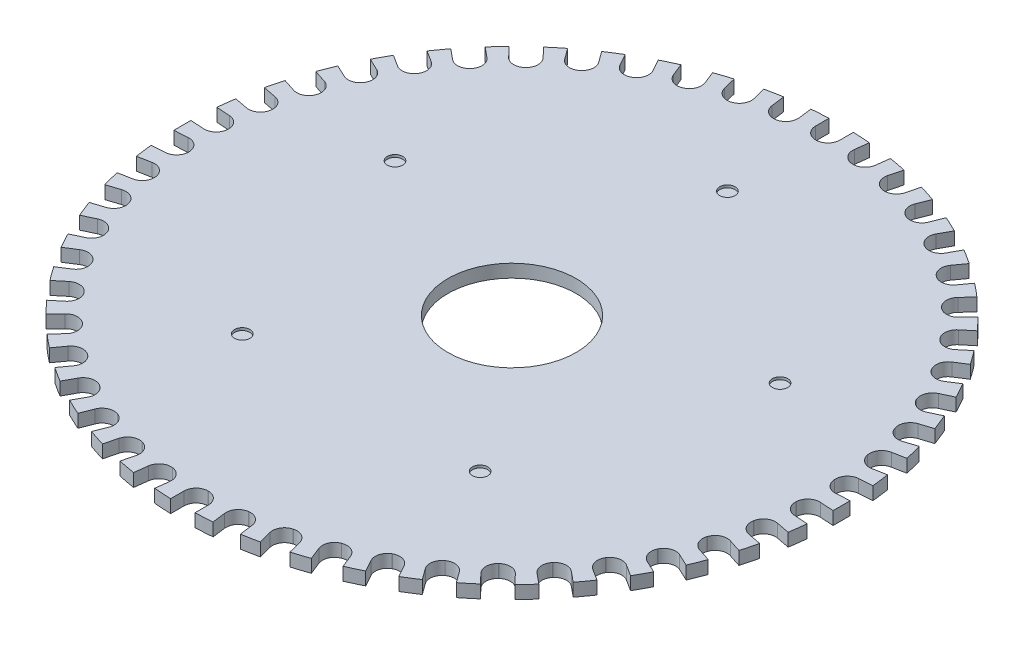
SolidWorks part; units mm, degrees
material "AISI 304"
ref_plane "Plano frontal" through (0, 0, 0) normal (0, 0, 1) x (1, 0, 0)
ref_plane "Plano superior" through (0, 0, 0) normal (0, 1, 0) x (1, 0, 0)
ref_plane "Plano direito" through (0, 0, 0) normal (1, 0, 0) x (0, 0, -1)
sketch "Esboço1" plane through (0, 0, 0) normal (0, 1, 0) x (1, 0, 0)
  line L0 (1.1332, 12.7999) -> (1.0679, 12.283)
  line L1 (-0.48, 12.841) -> (-0.48, 12.32)
  line L2 (0.47, 12.8414) -> (0.47, 12.32)
  line L3 (-0.01, 11.85) -> (0, 11.85)
  line L4 (2.0757, 12.6812) -> (2.0104, 12.1639)
  line L5 (1.4753, 11.7578) -> (1.4852, 11.7566)
  line L6 (2.7285, 12.557) -> (2.5989, 12.0523)
  line L7 (3.6488, 12.3211) -> (3.5191, 11.8161)
  line L8 (2.9373, 11.4802) -> (2.947, 11.4777)
  line L9 (4.2808, 12.116) -> (4.089, 11.6315)
  line L10 (5.1642, 11.7666) -> (4.9723, 11.2818)
  line L11 (4.353, 11.0215) -> (4.3623, 11.0179)
  line L12 (5.7656, 11.4839) -> (5.5146, 11.0273)
  line L13 (6.5983, 11.0266) -> (6.3471, 10.5697)
  line L14 (5.7, 10.3891) -> (5.7088, 10.3842)
  line L15 (7.1594, 10.6707) -> (6.8532, 10.2492)
  line L16 (7.9282, 10.1127) -> (7.6218, 9.6908)
  line L17 (6.9572, 9.5927) -> (6.9653, 9.5869)
  line L18 (8.4404, 9.6893) -> (8.0837, 9.3095)
  line L19 (9.1332, 9.0392) -> (8.7762, 8.6592)
  line L20 (8.1046, 8.6451) -> (8.1119, 8.6383)
  line L21 (9.5882, 8.555) -> (9.1868, 8.2229)
  line L22 (10.1941, 7.8233) -> (9.7923, 7.4909)
  line L23 (9.1242, 7.5612) -> (9.1306, 7.5535)
  line L24 (10.5848, 7.2858) -> (10.1449, 7.0067)
  line L25 (11.0942, 6.4839) -> (10.654, 6.2046)
  line L26 (9.9999, 6.358) -> (10.0053, 6.3495)
  line L27 (11.4145, 5.9018) -> (10.9431, 5.6799)
  line L28 (11.8194, 5.0423) -> (11.3476, 4.8203)
  line L29 (10.7179, 5.0545) -> (10.7222, 5.0455)
  line L30 (12.0642, 4.4246) -> (11.5687, 4.2636)
  line L31 (12.3581, 3.5212) -> (11.8623, 3.3601)
  line L32 (11.2669, 3.6714) -> (11.27, 3.6619)
  line L33 (12.5236, 2.8777) -> (12.0118, 2.78)
  line L34 (12.702, 1.9446) -> (12.1898, 1.8469)
  line L35 (11.6382, 2.2303) -> (11.6401, 2.2205)
  line L36 (12.7856, 1.2853) -> (12.2656, 1.2526)
  line L37 (12.8456, 0.3372) -> (12.3252, 0.3045)
  line L38 (11.826, 0.754) -> (11.8266, 0.7441)
  line L39 (12.8458, -0.3272) -> (12.3258, -0.2945)
  line L40 (12.7866, -1.2754) -> (12.2662, -1.2427)
  line L41 (11.8272, -0.7341) -> (11.8266, -0.7441)
  line L42 (12.7035, -1.9347) -> (12.1917, -1.837)
  line L43 (12.5259, -2.8679) -> (12.0137, -2.7702)
  line L44 (11.642, -2.2106) -> (11.6401, -2.2205)
  line L45 (12.3609, -3.5116) -> (11.8653, -3.3506)
  line L46 (12.0677, -4.4152) -> (11.5718, -4.2541)
  line L47 (11.2731, -3.6523) -> (11.27, -3.6619)
  line L48 (11.8233, -5.0331) -> (11.3518, -4.8113)
  line L49 (11.4191, -5.8929) -> (10.9474, -5.6709)
  line L50 (10.7265, -5.0364) -> (10.7222, -5.0455)
  line L51 (11.0992, -6.4753) -> (10.6593, -6.1961)
  line L52 (10.5905, -7.2776) -> (10.1503, -6.9982)
  line L53 (10.0106, -6.3411) -> (10.0053, -6.3495)
  line L54 (10.2001, -7.8153) -> (9.7987, -7.4832)
  line L55 (9.5949, -8.5476) -> (9.1931, -8.2152)
  line L56 (9.137, -7.5458) -> (9.1306, -7.5535)
  line L57 (9.1402, -9.0321) -> (8.7835, -8.6523)
  line L58 (8.4479, -9.6827) -> (8.091, -9.3026)
  line L59 (8.1192, -8.6314) -> (8.1119, -8.6383)
  line L60 (7.9361, -10.1065) -> (7.6298, -9.685)
  line L61 (7.1677, -10.6652) -> (6.8613, -10.2433)
  line L62 (6.9733, -9.581) -> (6.9653, -9.5869)
  line L63 (6.6068, -11.0214) -> (6.3558, -10.5649)
  line L64 (5.7745, -11.4794) -> (5.5233, -11.0225)
  line L65 (5.7175, -10.3794) -> (5.7088, -10.3842)
  line L66 (5.1734, -11.7626) -> (4.9816, -11.2781)
  line L67 (4.2902, -12.1127) -> (4.0983, -11.6279)
  line L68 (4.3716, -11.0142) -> (4.3623, -11.0179)
  line L69 (3.6584, -12.3182) -> (3.5288, -11.8136)
  line L70 (2.7383, -12.5548) -> (2.6086, -12.0498)
  line L71 (2.9567, -11.4752) -> (2.947, -11.4777)
  line L72 (2.0856, -12.6796) -> (2.0203, -12.1627)
  line L73 (1.1432, -12.7991) -> (1.0778, -12.2818)
  line L74 (1.4951, -11.7553) -> (1.4852, -11.7566)
  line L75 (0.48, -12.841) -> (0.48, -12.32)
  line L76 (-0.47, -12.8414) -> (-0.47, -12.32)
  line L77 (0.01, -11.85) -> (0, -11.85)
  line L78 (-1.1332, -12.7999) -> (-1.0679, -12.283)
  line L79 (-2.0757, -12.6812) -> (-2.0104, -12.1639)
  line L80 (-1.4753, -11.7578) -> (-1.4852, -11.7566)
  line L81 (-2.7285, -12.557) -> (-2.5989, -12.0523)
  line L82 (-3.6488, -12.3211) -> (-3.5191, -11.8161)
  line L83 (-2.9373, -11.4802) -> (-2.947, -11.4777)
  line L84 (-4.2808, -12.116) -> (-4.089, -11.6315)
  line L85 (-5.1642, -11.7666) -> (-4.9723, -11.2818)
  line L86 (-4.353, -11.0215) -> (-4.3623, -11.0179)
  line L87 (-5.7656, -11.4839) -> (-5.5146, -11.0273)
  line L88 (-6.5983, -11.0266) -> (-6.3471, -10.5697)
  line L89 (-5.7, -10.3891) -> (-5.7088, -10.3842)
  line L90 (-7.1594, -10.6707) -> (-6.8532, -10.2492)
  line L91 (-7.9282, -10.1127) -> (-7.6218, -9.6908)
  line L92 (-6.9572, -9.5927) -> (-6.9653, -9.5869)
  line L93 (-8.4404, -9.6893) -> (-8.0837, -9.3095)
  line L94 (-9.1332, -9.0392) -> (-8.7762, -8.6592)
  line L95 (-8.1046, -8.6451) -> (-8.1119, -8.6383)
  line L96 (-9.5882, -8.555) -> (-9.1868, -8.2229)
  line L97 (-10.1941, -7.8233) -> (-9.7923, -7.4909)
  line L98 (-9.1242, -7.5612) -> (-9.1306, -7.5535)
  line L99 (-10.5848, -7.2858) -> (-10.1449, -7.0067)
  line L100 (-11.0942, -6.4839) -> (-10.654, -6.2046)
  line L101 (-9.9999, -6.358) -> (-10.0053, -6.3495)
  line L102 (-11.4145, -5.9018) -> (-10.9431, -5.6799)
  line L103 (-11.8194, -5.0423) -> (-11.3476, -4.8203)
  line L104 (-10.7179, -5.0545) -> (-10.7222, -5.0455)
  line L105 (-12.0642, -4.4246) -> (-11.5687, -4.2636)
  line L106 (-12.3581, -3.5212) -> (-11.8623, -3.3601)
  line L107 (-11.2669, -3.6714) -> (-11.27, -3.6619)
  line L108 (-12.5236, -2.8777) -> (-12.0118, -2.78)
  line L109 (-12.702, -1.9446) -> (-12.1898, -1.8469)
  line L110 (-11.6382, -2.2303) -> (-11.6401, -2.2205)
  line L111 (-12.7856, -1.2853) -> (-12.2656, -1.2526)
  line L112 (-12.8456, -0.3372) -> (-12.3252, -0.3045)
  line L113 (-11.826, -0.754) -> (-11.8266, -0.7441)
  line L114 (-12.8458, 0.3272) -> (-12.3258, 0.2945)
  line L115 (-12.7866, 1.2754) -> (-12.2662, 1.2427)
  line L116 (-11.8272, 0.7341) -> (-11.8266, 0.7441)
  line L117 (-12.7035, 1.9347) -> (-12.1917, 1.837)
  line L118 (-12.5259, 2.8679) -> (-12.0137, 2.7702)
  line L119 (-11.642, 2.2106) -> (-11.6401, 2.2205)
  line L120 (-12.3609, 3.5116) -> (-11.8653, 3.3506)
  line L121 (-12.0677, 4.4152) -> (-11.5718, 4.2541)
  line L122 (-11.2731, 3.6523) -> (-11.27, 3.6619)
  line L123 (-11.8233, 5.0331) -> (-11.3518, 4.8113)
  line L124 (-11.4191, 5.8929) -> (-10.9474, 5.6709)
  line L125 (-10.7265, 5.0364) -> (-10.7222, 5.0455)
  line L126 (-11.0992, 6.4753) -> (-10.6593, 6.1961)
  line L127 (-10.5905, 7.2776) -> (-10.1503, 6.9982)
  line L128 (-10.0106, 6.3411) -> (-10.0053, 6.3495)
  line L129 (-10.2001, 7.8153) -> (-9.7987, 7.4832)
  line L130 (-9.5949, 8.5476) -> (-9.1931, 8.2152)
  line L131 (-9.137, 7.5458) -> (-9.1306, 7.5535)
  line L132 (-9.1402, 9.0321) -> (-8.7835, 8.6523)
  line L133 (-8.4479, 9.6827) -> (-8.091, 9.3026)
  line L134 (-8.1192, 8.6314) -> (-8.1119, 8.6383)
  line L135 (-7.9361, 10.1065) -> (-7.6298, 9.685)
  line L136 (-7.1677, 10.6652) -> (-6.8613, 10.2433)
  line L137 (-6.9733, 9.581) -> (-6.9653, 9.5869)
  line L138 (-6.6068, 11.0214) -> (-6.3558, 10.5649)
  line L139 (-5.7745, 11.4794) -> (-5.5233, 11.0225)
  line L140 (-5.7175, 10.3794) -> (-5.7088, 10.3842)
  line L141 (-5.1734, 11.7626) -> (-4.9816, 11.2781)
  line L142 (-4.2902, 12.1127) -> (-4.0983, 11.6279)
  line L143 (-4.3716, 11.0142) -> (-4.3623, 11.0179)
  line L144 (-3.6584, 12.3182) -> (-3.5288, 11.8136)
  line L145 (-2.7383, 12.5548) -> (-2.6086, 12.0498)
  line L146 (-2.9567, 11.4752) -> (-2.947, 11.4777)
  line L147 (-2.0856, 12.6796) -> (-2.0203, 12.1627)
  line L148 (-1.1432, 12.7991) -> (-1.0778, 12.2818)
  line L149 (-1.4951, 11.7553) -> (-1.4852, 11.7566)
  circle A0 centre (0, 0) radius 12.85
  arc A1 (0.47, 12.32) -> (0, 11.85) centre (0, 12.32) cw
  arc A2 (-0.48, 12.32) -> (-0.01, 11.85) centre (-0.01, 12.32) ccw
  arc A3 (2.0104, 12.1639) -> (1.4852, 11.7566) centre (1.5441, 12.2229) cw
  arc A4 (1.0679, 12.283) -> (1.4753, 11.7578) centre (1.5342, 12.2241) ccw
  arc A5 (3.5191, 11.8161) -> (2.947, 11.4777) centre (3.0639, 11.9329) cw
  arc A6 (2.5989, 12.0523) -> (2.9373, 11.4802) centre (3.0542, 11.9354) ccw
  arc A7 (4.9723, 11.2818) -> (4.3623, 11.0179) centre (4.5353, 11.4548) cw
  arc A8 (4.089, 11.6315) -> (4.353, 11.0215) centre (4.526, 11.4585) ccw
  arc A9 (6.3471, 10.5697) -> (5.7088, 10.3842) centre (5.9352, 10.7961) cw
  arc A10 (5.5146, 11.0273) -> (5.7, 10.3891) centre (5.9264, 10.8009) ccw
  arc A11 (7.6218, 9.6908) -> (6.9653, 9.5869) centre (7.2415, 9.9671) cw
  arc A12 (6.8532, 10.2492) -> (6.9572, 9.5927) centre (7.2334, 9.973) ccw
  arc A13 (8.7762, 8.6592) -> (8.1119, 8.6383) centre (8.4336, 8.9809) cw
  arc A14 (8.0837, 9.3095) -> (8.1046, 8.6451) centre (8.4263, 8.9877) ccw
  arc A15 (9.7923, 7.4909) -> (9.1306, 7.5535) centre (9.4927, 7.8531) cw
  arc A16 (9.1868, 8.2229) -> (9.1242, 7.5612) centre (9.4863, 7.8608) ccw
  arc A17 (10.654, 6.2046) -> (10.0053, 6.3495) centre (10.4021, 6.6014) cw
  arc A18 (10.1449, 7.0067) -> (9.9999, 6.358) centre (10.3968, 6.6098) ccw
  arc A19 (11.3476, 4.8203) -> (10.7222, 5.0455) centre (11.1475, 5.2456) cw
  arc A20 (10.9431, 5.6799) -> (10.7179, 5.0545) centre (11.1432, 5.2546) ccw
  arc A21 (11.8623, 3.3601) -> (11.27, 3.6619) centre (11.717, 3.8071) cw
  arc A22 (11.5687, 4.2636) -> (11.2669, 3.6714) centre (11.7139, 3.8166) ccw
  arc A23 (12.1898, 1.8469) -> (11.6401, 2.2205) centre (12.1018, 2.3085) cw
  arc A24 (12.0118, 2.78) -> (11.6382, 2.2303) centre (12.0999, 2.3184) ccw
  arc A25 (12.3252, 0.3045) -> (11.8266, 0.7441) centre (12.2957, 0.7736) cw
  arc A26 (12.2656, 1.2526) -> (11.826, 0.754) centre (12.2951, 0.7836) ccw
  arc A27 (12.2662, -1.2427) -> (11.8266, -0.7441) centre (12.2957, -0.7736) cw
  arc A28 (12.3258, -0.2945) -> (11.8272, -0.7341) centre (12.2963, -0.7636) ccw
  arc A29 (12.0137, -2.7702) -> (11.6401, -2.2205) centre (12.1018, -2.3085) cw
  arc A30 (12.1917, -1.837) -> (11.642, -2.2106) centre (12.1037, -2.2987) ccw
  arc A31 (11.5718, -4.2541) -> (11.27, -3.6619) centre (11.717, -3.8071) cw
  arc A32 (11.8653, -3.3506) -> (11.2731, -3.6523) centre (11.7201, -3.7976) ccw
  arc A33 (10.9474, -5.6709) -> (10.7222, -5.0455) centre (11.1475, -5.2456) cw
  arc A34 (11.3518, -4.8113) -> (10.7265, -5.0364) centre (11.1517, -5.2366) ccw
  arc A35 (10.1503, -6.9982) -> (10.0053, -6.3495) centre (10.4021, -6.6014) cw
  arc A36 (10.6593, -6.1961) -> (10.0106, -6.3411) centre (10.4075, -6.5929) ccw
  arc A37 (9.1931, -8.2152) -> (9.1306, -7.5535) centre (9.4927, -7.8531) cw
  arc A38 (9.7987, -7.4832) -> (9.137, -7.5458) centre (9.4991, -7.8454) ccw
  arc A39 (8.091, -9.3026) -> (8.1119, -8.6383) centre (8.4336, -8.9809) cw
  arc A40 (8.7835, -8.6523) -> (8.1192, -8.6314) centre (8.4409, -8.974) ccw
  arc A41 (6.8613, -10.2433) -> (6.9653, -9.5869) centre (7.2415, -9.9671) cw
  arc A42 (7.6298, -9.685) -> (6.9733, -9.581) centre (7.2496, -9.9612) ccw
  arc A43 (5.5233, -11.0225) -> (5.7088, -10.3842) centre (5.9352, -10.7961) cw
  arc A44 (6.3558, -10.5649) -> (5.7175, -10.3794) centre (5.944, -10.7913) ccw
  arc A45 (4.0983, -11.6279) -> (4.3623, -11.0179) centre (4.5353, -11.4548) cw
  arc A46 (4.9816, -11.2781) -> (4.3716, -11.0142) centre (4.5446, -11.4512) ccw
  arc A47 (2.6086, -12.0498) -> (2.947, -11.4777) centre (3.0639, -11.9329) cw
  arc A48 (3.5288, -11.8136) -> (2.9567, -11.4752) centre (3.0735, -11.9305) ccw
  arc A49 (1.0778, -12.2818) -> (1.4852, -11.7566) centre (1.5441, -12.2229) cw
  arc A50 (2.0203, -12.1627) -> (1.4951, -11.7553) centre (1.554, -12.2216) ccw
  arc A51 (-0.47, -12.32) -> (0, -11.85) centre (0, -12.32) cw
  arc A52 (0.48, -12.32) -> (0.01, -11.85) centre (0.01, -12.32) ccw
  arc A53 (-2.0104, -12.1639) -> (-1.4852, -11.7566) centre (-1.5441, -12.2229) cw
  arc A54 (-1.0679, -12.283) -> (-1.4753, -11.7578) centre (-1.5342, -12.2241) ccw
  arc A55 (-3.5191, -11.8161) -> (-2.947, -11.4777) centre (-3.0639, -11.9329) cw
  arc A56 (-2.5989, -12.0523) -> (-2.9373, -11.4802) centre (-3.0542, -11.9354) ccw
  arc A57 (-4.9723, -11.2818) -> (-4.3623, -11.0179) centre (-4.5353, -11.4548) cw
  arc A58 (-4.089, -11.6315) -> (-4.353, -11.0215) centre (-4.526, -11.4585) ccw
  arc A59 (-6.3471, -10.5697) -> (-5.7088, -10.3842) centre (-5.9352, -10.7961) cw
  arc A60 (-5.5146, -11.0273) -> (-5.7, -10.3891) centre (-5.9264, -10.8009) ccw
  arc A61 (-7.6218, -9.6908) -> (-6.9653, -9.5869) centre (-7.2415, -9.9671) cw
  arc A62 (-6.8532, -10.2492) -> (-6.9572, -9.5927) centre (-7.2334, -9.973) ccw
  arc A63 (-8.7762, -8.6592) -> (-8.1119, -8.6383) centre (-8.4336, -8.9809) cw
  arc A64 (-8.0837, -9.3095) -> (-8.1046, -8.6451) centre (-8.4263, -8.9877) ccw
  arc A65 (-9.7923, -7.4909) -> (-9.1306, -7.5535) centre (-9.4927, -7.8531) cw
  arc A66 (-9.1868, -8.2229) -> (-9.1242, -7.5612) centre (-9.4863, -7.8608) ccw
  arc A67 (-10.654, -6.2046) -> (-10.0053, -6.3495) centre (-10.4021, -6.6014) cw
  arc A68 (-10.1449, -7.0067) -> (-9.9999, -6.358) centre (-10.3968, -6.6098) ccw
  arc A69 (-11.3476, -4.8203) -> (-10.7222, -5.0455) centre (-11.1475, -5.2456) cw
  arc A70 (-10.9431, -5.6799) -> (-10.7179, -5.0545) centre (-11.1432, -5.2546) ccw
  arc A71 (-11.8623, -3.3601) -> (-11.27, -3.6619) centre (-11.717, -3.8071) cw
  arc A72 (-11.5687, -4.2636) -> (-11.2669, -3.6714) centre (-11.7139, -3.8166) ccw
  arc A73 (-12.1898, -1.8469) -> (-11.6401, -2.2205) centre (-12.1018, -2.3085) cw
  arc A74 (-12.0118, -2.78) -> (-11.6382, -2.2303) centre (-12.0999, -2.3184) ccw
  arc A75 (-12.3252, -0.3045) -> (-11.8266, -0.7441) centre (-12.2957, -0.7736) cw
  arc A76 (-12.2656, -1.2526) -> (-11.826, -0.754) centre (-12.2951, -0.7836) ccw
  arc A77 (-12.2662, 1.2427) -> (-11.8266, 0.7441) centre (-12.2957, 0.7736) cw
  arc A78 (-12.3258, 0.2945) -> (-11.8272, 0.7341) centre (-12.2963, 0.7636) ccw
  arc A79 (-12.0137, 2.7702) -> (-11.6401, 2.2205) centre (-12.1018, 2.3085) cw
  arc A80 (-12.1917, 1.837) -> (-11.642, 2.2106) centre (-12.1037, 2.2987) ccw
  arc A81 (-11.5718, 4.2541) -> (-11.27, 3.6619) centre (-11.717, 3.8071) cw
  arc A82 (-11.8653, 3.3506) -> (-11.2731, 3.6523) centre (-11.7201, 3.7976) ccw
  arc A83 (-10.9474, 5.6709) -> (-10.7222, 5.0455) centre (-11.1475, 5.2456) cw
  arc A84 (-11.3518, 4.8113) -> (-10.7265, 5.0364) centre (-11.1517, 5.2366) ccw
  arc A85 (-10.1503, 6.9982) -> (-10.0053, 6.3495) centre (-10.4021, 6.6014) cw
  arc A86 (-10.6593, 6.1961) -> (-10.0106, 6.3411) centre (-10.4075, 6.5929) ccw
  arc A87 (-9.1931, 8.2152) -> (-9.1306, 7.5535) centre (-9.4927, 7.8531) cw
  arc A88 (-9.7987, 7.4832) -> (-9.137, 7.5458) centre (-9.4991, 7.8454) ccw
  arc A89 (-8.091, 9.3026) -> (-8.1119, 8.6383) centre (-8.4336, 8.9809) cw
  arc A90 (-8.7835, 8.6523) -> (-8.1192, 8.6314) centre (-8.4409, 8.974) ccw
  arc A91 (-6.8613, 10.2433) -> (-6.9653, 9.5869) centre (-7.2415, 9.9671) cw
  arc A92 (-7.6298, 9.685) -> (-6.9733, 9.581) centre (-7.2496, 9.9612) ccw
  arc A93 (-5.5233, 11.0225) -> (-5.7088, 10.3842) centre (-5.9352, 10.7961) cw
  arc A94 (-6.3558, 10.5649) -> (-5.7175, 10.3794) centre (-5.944, 10.7913) ccw
  arc A95 (-4.0983, 11.6279) -> (-4.3623, 11.0179) centre (-4.5353, 11.4548) cw
  arc A96 (-4.9816, 11.2781) -> (-4.3716, 11.0142) centre (-4.5446, 11.4512) ccw
  arc A97 (-2.6086, 12.0498) -> (-2.947, 11.4777) centre (-3.0639, 11.9329) cw
  arc A98 (-3.5288, 11.8136) -> (-2.9567, 11.4752) centre (-3.0735, 11.9305) ccw
  arc A99 (-1.0778, 12.2818) -> (-1.4852, 11.7566) centre (-1.5441, 12.2229) cw
  arc A100 (-2.0203, 12.1627) -> (-1.4951, 11.7553) centre (-1.554, 12.2216) ccw
  point P4 (-0.475, 12.85)
  point P5 (-0.48, 11.85)
  point P6 (0.475, 12.85)
  point P7 (0.47, 11.85)
  dimension "D1" = 25.7
  dimension "D5" = 0.47
  dimension "D4" = 11.85
  dimension "D2" = 0.95
  dimension "D3" = 50
  dimension "D6" = 1.5441
  dimension "D7" = 0.6645
extrude "Ressalto-extrusão1" add sketch "Esboço1" along normal mid plane 0.5058 contours A100 L147 A0 L145 A97 L146 A98 L144 L142 A95 L143 A96 L141 L139 A93 L140 A94 L138 L136 A91 L137 A92 L135 L133 A89 L134 A90 L132 L130 A87 L131 A88 L129 L127 A85 L128 A86 L126 L124 A83 L125 A84 L123 region at (0, 0, 0)
sketch "Esboço2" plane through (0, 0.2529, 0) normal (0, 1, 0) x (1, 0, 0)
  circle A0 centre (0, 0) radius 2.5
  dimension "D1" = 5
extrude "Corte-extrusão1" cut sketch "Esboço2" against normal through all
sketch "Esboço3" plane through (0, 0.2529, 0) normal (0, 1, 0) x (1, 0, 0)
  circle A0 centre (0, 8.4) radius 0.3
  circle A1 centre (7.5078, 2.9452) radius 0.3
  circle A2 centre (4.6401, -5.8807) radius 0.3
  circle A3 centre (-4.6401, -5.8807) radius 0.3
  circle A4 centre (-7.5078, 2.9452) radius 0.3
  dimension "D1" = 0.6
  dimension "D2" = 8.4
  dimension "D3" = 5
extrude "Corte-extrusão2" cut sketch "Esboço3" against normal blind 0.1
mirror "Espelhar1" about plane through (0, 0, 0) normal (0, 1, 0) of "Corte-extrusão2"
